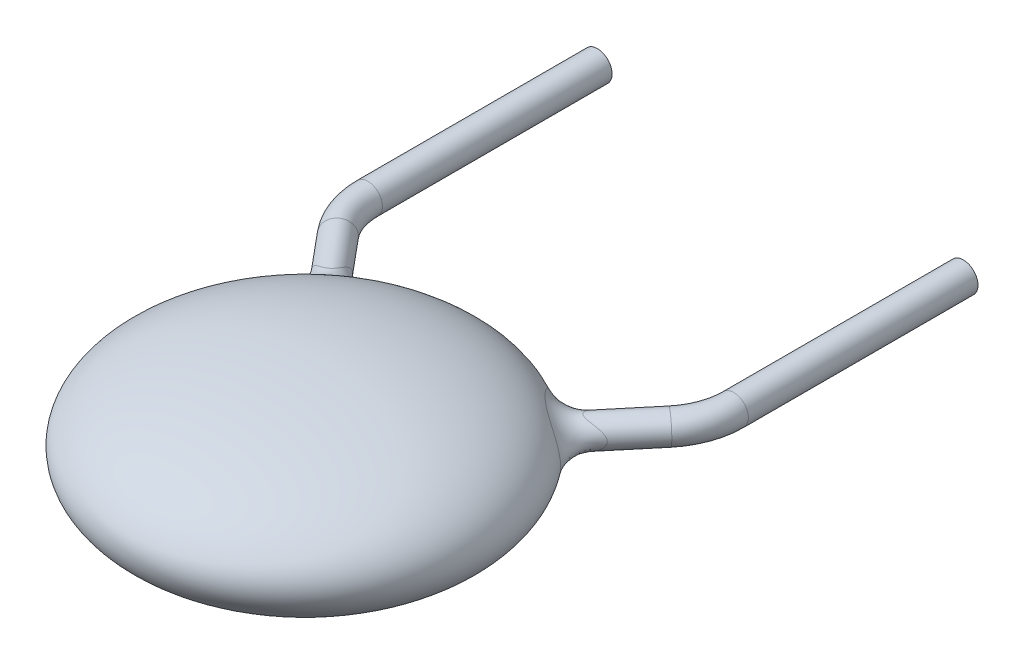
SolidWorks part; units mm, degrees
ref_plane "Front Plane" through (0, 0, 0) normal (0, 0, 1) x (1, 0, 0)
ref_plane "Top Plane" through (0, 0, 0) normal (0, 1, 0) x (1, 0, 0)
ref_plane "Right Plane" through (0, 0, 0) normal (1, 0, 0) x (0, 0, -1)
sketch "Sketch3" plane through (0, 0, 0) normal (1, 0, 0) x (0, 0, -1)
  line L7 (-4.5, 1) -> (-4.5, -1)
  ellipse E0 centre (-4.5, 0) end of major axis (-2, 0) minor radius 1 (-4.5, 1) -> (-4.5, -1) cw
  point P11 (-4.5, 0)
  dimension "D1" = 5
  dimension "D2" = 2
  dimension "D3" = 2
revolve "Revolve1" add sketch "Sketch3" angle 360 mid plane about L7
sketch "Sketch149" plane through (0, 0, 0) normal (0, 0, 1) x (1, 0, 0)
  line L0 (-2.5, 0) -> (2.5, 0) construction
  circle A0 centre (-2.5, 0) radius 0.2
  point P2 (0, 0)
  dimension "D3" = 0.4
  dimension "D1" = 5
sketch "Sketch150" plane through (0, 0, 0) normal (0, 1, 0) x (1, 0, 0)
  line L0 (-2.5, 2) -> (-2.5, -1.138)
  line L2 (-2.2682, -1.7781) -> (0, -4.5)
  line L3 (0, -4.5) -> (2.2682, -1.7781)
  line L4 (2.5, -1.138) -> (2.5, 2)
  arc A0 (2.2682, -1.7781) -> (2.5, -1.138) centre (1.5, -1.138) ccw
  arc A1 (-2.5, -1.138) -> (-2.2682, -1.7781) centre (-1.5, -1.138) ccw
  point P19 (2.5, -1.5)
  point P22 (-2.5, -1.5)
  dimension "D3" = 1
  dimension "D1" = 2
  dimension "D2" = 0.5
sweep "Sweep1" add profiles "Sketch149" path "Sketch150"
fillet "Fillet1" radius 0.5 2 edges at (1.4427, 0.0287, 2.4596) (-1.4427, -0.0287, 2.4596)
